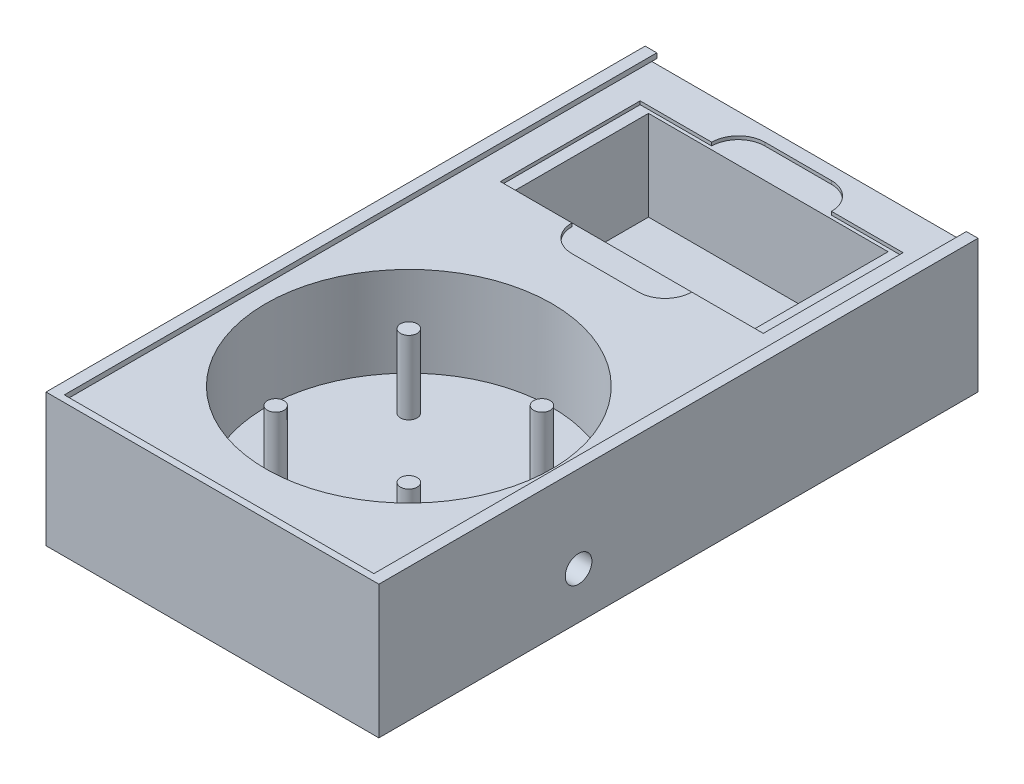
SolidWorks part; units mm, degrees
ref_plane "Front Plane" through (0, 0, 0) normal (0, 0, 1) x (1, 0, 0)
ref_plane "Top Plane" through (0, 0, 0) normal (0, 1, 0) x (1, 0, 0)
ref_plane "Right Plane" through (0, 0, 0) normal (1, 0, 0) x (0, 0, -1)
sketch "草图1" plane through (0, 0, 0) normal (0, 1, 0) x (1, 0, 0)
  line L1 (-50, -90) -> (50, -90)
  line L2 (-50, -90) -> (-50, 90)
  line L3 (-50, 90) -> (50, 90)
  line L4 (50, -90) -> (50, 90)
  line L5 (-50, -90) -> (50, 90) construction
  line L6 (-50, 90) -> (50, -90) construction
  point P0 (0, 0)
  dimension "D1" = 100
  dimension "D2" = 180
extrude "凸台-拉伸1" add sketch "草图1" along normal blind 40
sketch "草图2" plane through (0, 40, 0) normal (0, 1, 0) x (1, 0, 0)
  line L0 (0, -103.2924) -> (0, 143.3074) construction
  line L1 (-39.5, 36) -> (39.5, 36)
  line L2 (-39.5, 36) -> (-39.5, 78)
  line L3 (-39.5, 78) -> (39.5, 78)
  line L4 (39.5, 36) -> (39.5, 78)
  line L5 (-39.5, 36) -> (39.5, 78) construction
  line L6 (-39.5, 78) -> (39.5, 36) construction
  line L7 (50, 90) -> (-50, 90) construction
  circle A0 centre (0, -31) radius 43
  point P0 (0, 57)
  dimension "D3" = 86
  dimension "D4" = 24
  dimension "D1" = 79
  dimension "D2" = 42
  dimension "D5" = 12
extrude "切除-拉伸1" cut sketch "草图2" against normal blind 4 contours L1 L4 L3 L2 | L2 L1 L4 L3 region at (0, 40, -57)
sketch "草图3" plane through (0, 36, 0) normal (0, 1, 0) x (1, 0, 0)
  line L0 (0, -98.5472) -> (0, 107.168) construction
  line L1 (-39.5, 78) -> (39.5, 78) construction
  line L2 (-36, 37) -> (36, 37)
  line L3 (-36, 37) -> (-36, 77)
  line L4 (-36, 77) -> (36, 77)
  line L5 (36, 37) -> (36, 77)
  line L6 (-36, 37) -> (36, 77) construction
  line L7 (-36, 77) -> (36, 37) construction
  point P2 (0, 57)
  dimension "D1" = 72
  dimension "D2" = 40
  dimension "D3" = 1
extrude "切除-拉伸2" cut sketch "草图3" against normal blind 27
extrude "切除-拉伸3" cut sketch "草图2<3>" against normal blind 30 contours A0
sketch "草图2<3>" plane through (0, 40, 0) normal (0, 1, 0) x (1, 0, 0) same geometry as "草图2"
sketch "草图4" plane through (50, 0, 0) normal (1, 0, 0) x (0, 0, -1)
  line L0 (-90, 40) -> (-90, 0) construction
  line L1 (-90, 0) -> (90, 0) construction
  circle A0 centre (-30, 14) radius 4
  dimension "D1" = 8
  dimension "D2" = 60
  dimension "D3" = 14
extrude "切除-拉伸4" cut sketch "草图4" against normal up to surface (7.2917 mm away) up to face at (0, 10, 74)
sketch "草图5" plane through (0, 10, 0) normal (0, 1, 0) x (1, 0, 0)
  line L0 (0, -137.8524) -> (0, 122.5422) construction
  line L1 (-43, -31) -> (43, -31) construction
  circle A0 centre (-20, -11) radius 2.5
  circle A1 centre (20, -11) radius 2.5
  circle A2 centre (0, -31) radius 43 construction
  circle A3 centre (0, -31) radius 43 construction
  circle A4 centre (-20, -51) radius 2.5
  circle A5 centre (20, -51) radius 2.5
  dimension "D1" = 5
  dimension "D2" = 40
  dimension "D3" = 40
extrude "凸台-拉伸2" add sketch "草图5" along normal blind 22
sketch "草图6" plane through (0, 40, 0) normal (0, 1, 0) x (1, 0, 0)
  line L0 (0, 113.4579) -> (0, -23.9307) construction
  line L2 (-10, 78) -> (10, 78) construction
  line L3 (-39.5, 78) -> (39.5, 78) construction
  line L4 (-10, 86) -> (10, 86)
  line L5 (-10, 70) -> (10, 70)
  line L6 (-39.5, 57) -> (39.5, 57) construction
  line L7 (-39.5, 36) -> (-39.5, 78) construction
  line L8 (39.5, 36) -> (39.5, 78) construction
  line L9 (-10, 36) -> (10, 36) construction
  line L10 (-10, 28) -> (10, 28)
  line L11 (-10, 44) -> (10, 44)
  arc A1 (-10, 86) -> (-10, 70) centre (-10, 78) ccw
  arc A2 (10, 70) -> (10, 86) centre (10, 78) ccw
  arc A3 (-10, 28) -> (-10, 44) centre (-10, 36) cw
  arc A4 (10, 44) -> (10, 28) centre (10, 36) cw
  point P7 (0, 78)
  point P20 (0, 36)
  dimension "D1" = 8
  dimension "D2" = 20
extrude "切除-拉伸5" cut sketch "草图6" against normal blind 4
sketch "草图8" plane through (0, 0, -90) normal (0, 0, -1) x (-1, 0, 0)
  line L0 (0, -12.4082) -> (0, 49.6461) construction
  line L2 (-50, 40) -> (50, 40) construction
  line L3 (-48.5, 37) -> (48.5, 37)
  line L5 (46.5041, 40) -> (-46.5, 40)
  line L6 (-46.5, 40) -> (-46.5, 38.5)
  line L7 (-46.5, 38.5) -> (-48.5, 38.5)
  line L8 (-48.5, 38.5) -> (-48.5, 37)
  line L9 (48.5, 38.5) -> (48.5, 37)
  line L10 (46.5, 38.5) -> (48.5, 38.5)
  line L11 (46.5, 40) -> (46.5, 38.5)
  line L12 (-50, 40) -> (-50, 0) construction
  line M10 (50, 40) -> (-50, 40)
  dimension "D1" = 1.5
  dimension "D2" = 1.5
  dimension "D3" = 2
extrude "切除-拉伸6" cut sketch "草图8" against normal offset from surface (178 mm away) 2 from offset 0 contours L0 L3 L9 L10 L11 L5 | L3 L0 L6 L7 L8 M10 region at (23.7605, 38.4842, -90) region at (-23.7605, 38.4842, -90) up to face at (0, 20, 90)
